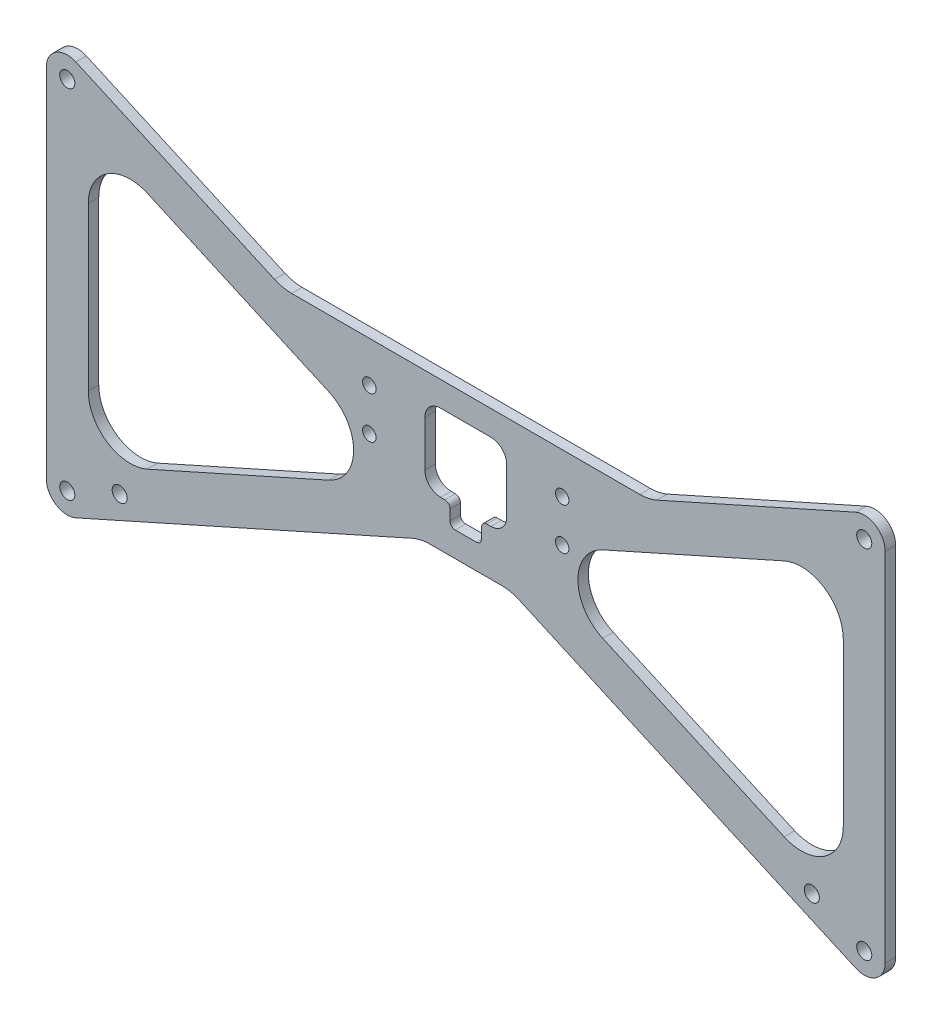
SolidWorks part; units mm, degrees
ref_plane "Front Plane" through (0, 0, 0) normal (0, 0, 1) x (1, 0, 0)
ref_plane "Top Plane" through (0, 0, 0) normal (0, 1, 0) x (1, 0, 0)
ref_plane "Right Plane" through (0, 0, 0) normal (1, 0, 0) x (0, 0, -1)
sketch "Sketch1" plane through (0, 0, 0) normal (0, 0, 1) x (1, 0, 0)
  line L0 (-120.65, -53.975) -> (120.65, 53.975) construction
  line L3 (-114.3, -44.1777) -> (-15.5498, 0)
  line L10 (-118.0569, -59.7714) -> (-13.6323, -13.0552)
  line L11 (-120.65, 53.975) -> (120.65, -53.975) construction
  line L12 (-118.0569, 59.7714) -> (-55.4208, 31.75)
  line L13 (-114.3, 44.1777) -> (-15.5498, 0)
  line L14 (55.4208, 31.75) -> (118.0569, 59.7714)
  line L15 (13.6323, -13.0552) -> (118.0569, -59.7714)
  line L16 (15.5498, 0) -> (114.3, 44.1777)
  line L17 (15.5498, 0) -> (114.3, -44.1777)
  line L18 (-127, 53.975) -> (-127, -53.975)
  line L19 (-114.3, 44.1777) -> (-114.3, -44.1777)
  line L20 (127, 53.975) -> (127, -53.975)
  line L21 (114.3, 44.1777) -> (114.3, -44.1777)
  line L24 (-55.4208, 31.75) -> (55.4208, 31.75)
  line L25 (-13.6323, -13.0552) -> (13.6323, -13.0552)
  arc A4 (-127, -53.975) -> (-118.0569, -59.7714) centre (-120.65, -53.975) ccw
  arc A5 (127, 53.975) -> (118.0569, 59.7714) centre (120.65, 53.975) ccw
  arc A6 (-118.0569, 59.7714) -> (-127, 53.975) centre (-120.65, 53.975) ccw
  arc A7 (118.0569, -59.7714) -> (127, -53.975) centre (120.65, -53.975) ccw
  point P2 (0, 0)
  point P9 (0, 0)
  point P13 (0, 0)
  point P26 (0, 0)
  dimension "D1" = 254
  dimension "D3" = 6.35
  dimension "D2" = 107.95
  dimension "D4" = 13.0552
  dimension "D6" = 31.75
extrude "Boss-Extrude1" add sketch "Sketch1" along normal blind 3.175
sketch "Sketch2" plane through (0, 0, 3.175) normal (0, 0, 1) x (1, 0, 0)
  line L0 (127, -53.975) -> (127, 53.975) construction
  line L1 (-127, 53.975) -> (-127, -53.975) construction
  line L2 (-107.3681, -41.0766) -> (-102.1819, -52.6694) construction
  line L3 (-114.3, -44.1777) -> (-15.5498, 0) construction
  line L4 (-118.0569, -59.7714) -> (-13.6323, -13.0552) construction
  circle A0 centre (-120.65, 53.975) radius 2.286
  circle A1 centre (-120.65, -53.975) radius 2.286
  circle A2 centre (120.65, -53.975) radius 2.286
  circle A3 centre (120.65, 53.975) radius 2.286
  arc A4 (-118.0569, 59.7714) -> (-127, 53.975) centre (-120.65, 53.975) ccw construction
  arc A5 (-127, -53.975) -> (-118.0569, -59.7714) centre (-120.65, -53.975) ccw construction
  arc A6 (118.0569, -59.7714) -> (127, -53.975) centre (120.65, -53.975) ccw construction
  arc A7 (127, 53.975) -> (118.0569, 59.7714) centre (120.65, 53.975) ccw construction
  circle A8 centre (104.775, -46.873) radius 2.286
  circle A9 centre (-104.775, -46.873) radius 2.286
  point P24 (-104.775, -46.873)
  dimension "D1" = 4.572
  dimension "D2" = 22.225
  dimension "D3" = 22.225
extrude "Cut-Extrude1" cut sketch "Sketch2" against normal through all
fillet "Fillet1" radius 12.7 10 edges at (114.3, -44.1777, 1.5875) (114.3, 44.1777, 1.5875) (15.5498, 0, 1.5875) (-114.3, -44.1777, 1.5875) (-15.5498, 0, 1.5875) (-114.3, 44.1777, 1.5875) (-55.4208, 31.75, 1.5875) (55.4208, 31.75, 1.5875) (13.6323, -13.0552, 1.5875) (-13.6323, -13.0552, 1.5875)
sketch "Sketch3" plane through (0, 0, 3.175) normal (0, 0, 1) x (1, 0, 0)
  line L1 (-12.3825, 24.2094) -> (12.3825, 24.2094)
  line L2 (-12.3825, 24.2094) -> (-12.3825, 0.8334)
  line L4 (12.3825, 24.2094) -> (12.3825, 0.8334)
  line L8 (-12.3825, 0.8334) -> (-4.7625, 0.8334)
  line L9 (-4.7625, 0.8334) -> (-4.7625, -5.5166)
  line L10 (-4.7625, -5.5166) -> (4.7625, -5.5166)
  line L11 (4.7625, -5.5166) -> (4.7625, 0.8334)
  line L12 (4.7625, 0.8334) -> (12.3825, 0.8334)
  line L13 (52.7095, 31.75) -> (-52.7095, 31.75) construction
  line L14 (0, 0) -> (-4.7625, 0) construction
  line L15 (0, 0) -> (4.7625, 0) construction
  dimension "D1" = 6.35
  dimension "D2" = 24.765
  dimension "D3" = 9.525
  dimension "D4" = 7.5406
  dimension "D5" = 23.3759
  dimension "D6" = 5.5166
extrude "Cut-Extrude2" cut sketch "Sketch3" against normal through all
fillet "Fillet2" radius 1.5875 4 edges at (4.7625, -5.5166, 1.5875) (-4.7625, -5.5166, 1.5875) (4.7625, 0.8334, 1.5875) (-4.7625, 0.8334, 1.5875)
fillet "Fillet3" radius 4.7625 4 edges at (12.3825, 0.8334, 1.5875) (12.3825, 24.2094, 1.5875) (-12.3825, 0.8334, 1.5875) (-12.3825, 24.2094, 1.5875)
sketch "Sketch4" plane through (0, 0, 0) normal (0, 0, -1) x (-1, 0, 0)
  circle A0 centre (29.1911, 19.407) radius 2.032
  circle A1 centre (29.1911, 6.707) radius 2.032
  circle A2 centre (-29.1911, 6.707) radius 2.032
  circle A3 centre (-29.1911, 19.407) radius 2.032
  point P12 (-28.575, 6.707)
  point P13 (-29.1911, 19.407)
  point P15 (-29.1911, 6.707)
  point P17 (29.1911, 19.407)
  dimension "D1" = 4.064
extrude "Cut-Extrude3" cut sketch "Sketch4" against normal through all
